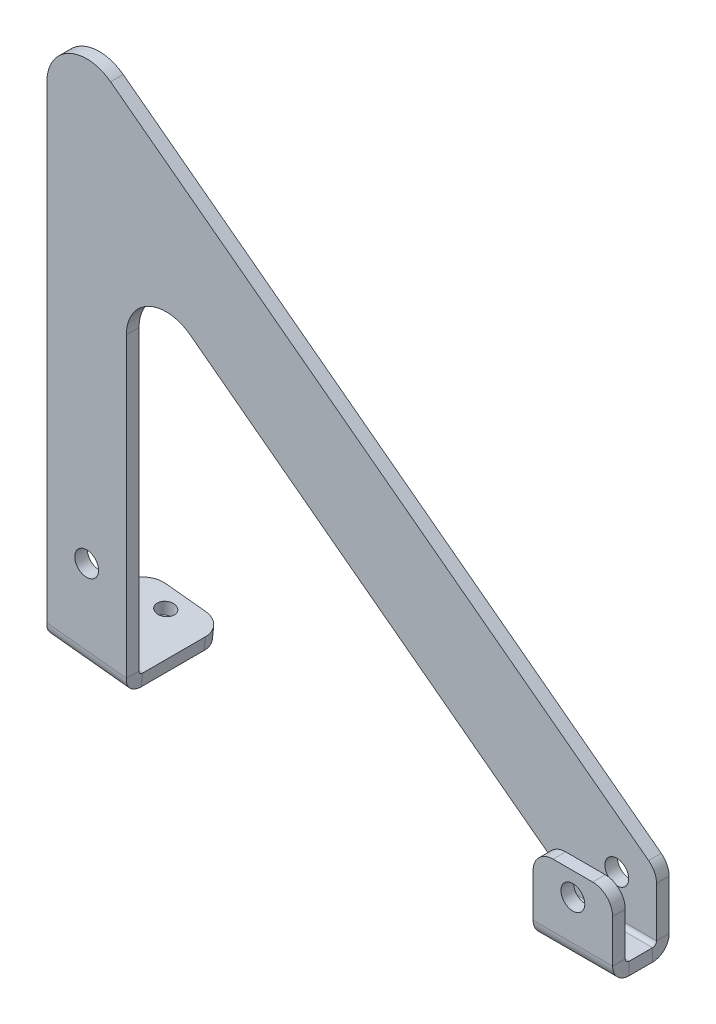
SolidWorks part; units mm, degrees
note: The reader was unsure of these and kept them because the rebuilt part matched: flange length of "Edge-Flange3", "Edge-Flange4", "Edge-Flange5".
ref_plane "Front Plane" through (0, 0, 0) normal (0, 0, 1) x (1, 0, 0)
ref_plane "Top Plane" through (0, 0, 0) normal (0, 1, 0) x (1, 0, 0)
ref_plane "Right Plane" through (0, 0, 0) normal (1, 0, 0) x (0, 0, -1)
sketch "Sketch1" plane through (0, 0, 0) normal (0, 0, 1) x (1, 0, 0)
  line L0 (0, 0) -> (0, 110) construction
  line L1 (0, 110) -> (141.3585, 3.4787) construction
  line L2 (10, 0) -> (10, 84.9289)
  line L3 (10, 89.9431) -> (130.0262, -0.5031) construction
  line L4 (-10, 0) -> (-10, 130.0569)
  line L5 (-10, 130.0569) -> (143.3721, 14.4827)
  line L6 (-10, 0) -> (10, 0)
  line L8 (123.3721, -0.5031) -> (10, 84.9289)
  line L9 (123.3721, -0.5031) -> (143.3721, -0.5031)
  line L12 (143.3721, -0.5031) -> (143.3721, 14.4827)
  line L15 (-10, 130.0569) -> (147.3766, 11.4651) construction
  line L16 (10, 89.9431) -> (135.3403, -4.5076) construction
  line L17 (10, 0) -> (10, 89.9431) construction
  circle A0 centre (133.3721, 9.4969) radius 3 construction
  circle A1 centre (0, 10) radius 3 construction
  dimension "D8" = 6
  dimension "D1" = 110
  dimension "D2" = 177
  dimension "D3" = 53
  dimension "D6" = 10
  dimension "D7" = 10
  dimension "D9" = 10
  dimension "D10" = 10
  dimension "D11" = 20
  dimension "D4" = 10
  dimension "D5" = 10
base flange "Base-Flange1" sketch "Sketch1" thickness 3.175 reverse thickness direction no parameters "D1"=1
sketch "Sketch12" plane through (0, 0, 0) normal (0, 0, 1) x (1, 0, 0)
  line L0 (-10, 0) -> (10, 0) construction
  line L1 (0, 10) -> (0, 110)
  line L2 (0, 110) -> (133.3721, 9.4969)
  line L3 (143.3721, 14.4827) -> (-10, 130.0569) construction
  circle A0 centre (133.3721, 9.4969) radius 3
  circle A1 centre (0, 10) radius 3
  dimension "D3" = 6
  dimension "D1" = 10
  dimension "D2" = 100
  dimension "D4" = 167
edge flange "Edge-Flange3" sketch "Sketch15" flange angle 90 flange length 14.23 flange position bend outside bend radius 1 thickness 3.175 parameters "D6"=10
sketch "Sketch15" plane through (0, -0.5031, 0) normal (0, -1, 0) x (1, 0, 0)
  line L0 (123.3721, 0) -> (143.3721, 0) construction
  line L1 (123.3721, 0) -> (143.3721, 0)
  line L2 (123.3721, 0) -> (123.3721, 11.055)
  line L3 (123.3721, 11.055) -> (143.3721, 11.055)
  line L4 (143.3721, 11.055) -> (143.3721, 0)
bend "EdgeBend3" bend radius 1 bend angle 90 parameters "D5"=1
edge flange "Edge-Flange4" sketch "Sketch18" flange angle 90 flange length 20 flange position material inside bend radius 1 thickness 3.175 parameters "D6"=10
sketch "Sketch18" plane through (0, -1.5031, 11.055) normal (0, 0, 1) x (1, 0, 0)
  line L0 (143.3721, 0) -> (123.3721, 0) construction
  line L1 (143.3721, 0) -> (123.3721, 0)
  line L2 (123.3721, 0) -> (123.3721, 16.825)
  line L3 (123.3721, 16.825) -> (143.3721, 16.825)
  line L4 (143.3721, 16.825) -> (143.3721, 0)
bend "EdgeBend4" bend radius 1 bend angle 90 parameters "D5"=2
extrude "Cut-Extrude1" cut sketch "Sketch12" along normal through all both and the other way through all contours A0 | A1
sketch "Sketch19" plane through (0, 0, 0) normal (0, 0, 1) x (1, 0, 0)
  line L0 (-10, 0) -> (10, 0)
  line L1 (-10, 0) -> (-10, -7.8979)
  line L2 (10, 0) -> (10, -10)
  line L3 (-10, -7.8979) -> (10, -10)
  point P0 (-10, -6.9136)
  dimension "D1" = 10
  dimension "D2" = 84
base flange "Tab1" sketch "Sketch19" thickness 3.175 reverse thickness direction no parameters "D1"=1
edge flange "Edge-Flange5" sketch "Sketch24" flange angle 90 flange length 25 flange position bend outside bend radius 1 thickness 3.175 parameters "D6"=10
sketch "Sketch24" plane through (-0.9303, -8.8512, -3.175) normal (-0.1045, -0.9945, 0) x (-0.9945, 0.1045, 0)
  line L0 (9.1197, 0) -> (-10.9905, 0) construction
  line L1 (9.1197, 0) -> (-10.9905, 0)
  line L2 (-10.9905, 0) -> (-10.9905, 21.825)
  line L3 (-10.9905, 21.825) -> (9.1197, 21.825)
  line L4 (9.1197, 21.825) -> (9.1197, 0)
bend "EdgeBend5" bend radius 1 bend angle 90 parameters "D5"=3
fillet "Fillet1" radius 10 2 edges at (-10, 130.0569, -1.5875) (10, 84.9289, -1.5875)
fillet "Fillet2" radius 5 5 edges at (143.3721, 14.4827, -1.5875) (123.3721, 15.3219, 9.4675) (143.3721, 15.3219, 9.4675) (-10.2705, -10.4712, -25) (9.7295, -12.5733, -25)
sketch "Sketch27" plane through (-1.0348, -9.8457, 0) normal (0.1045, 0.9945, 0) x (0.9945, -0.1045, 0)
  line L4 (5.9905, 25) -> (-4.1197, 25)
  line L5 (-9.1197, 20) -> (-9.1197, 4.175)
  line L6 (-9.1197, 4.175) -> (10.9905, 4.175)
  line L7 (10.9905, 4.175) -> (10.9905, 20)
  line L8 (5.9905, 25) -> (-4.1197, 25)
  line L9 (-9.1197, 20) -> (-9.1197, 4.175)
  line L10 (-9.1197, 4.175) -> (10.9905, 4.175)
  line L11 (10.9905, 4.175) -> (10.9905, 20)
  circle A1 centre (0.9354, 20) radius 2.1554
  arc A2 (-4.1197, 25) -> (-9.1197, 20) centre (-4.1197, 20) ccw
  arc A3 (10.9905, 20) -> (5.9905, 25) centre (5.9905, 20) ccw
  arc A4 (-4.1197, 25) -> (-9.1197, 20) centre (-4.1197, 20) ccw
  arc A5 (10.9905, 20) -> (5.9905, 25) centre (5.9905, 20) ccw
  circle A6 centre (0.9354, 10) radius 2.1554
  point P15 (0.9354, 25)
  dimension "D2" = 4.3108
  dimension "D3" = 10
  dimension "D4" = 5
  dimension "D1" = 0
extrude "Cut-Extrude2" cut sketch "Sketch27" against normal through all contours A1 | A6
sketch "Bend-Lines1" [suppressed] plane through (0, 0, 0) normal (0, 1, 0) x (1, 0, 0)
sketch "Bounding-Box1" [suppressed] plane through (0, 0, 0) normal (0, 1, 0) x (1, 0, 0)
sheet metal parameters "Sheet-Metal1" thickness 3.175 parameters "D1"=1
flat pattern "Flat-Pattern1" [suppressed]
sketch "Bend-Lines2" plane through (0, 0, 0) normal (0, 1, 0) x (1, 0, 0)
sketch3d "Bounding-Box2" [suppressed]
  line L0 (-10, 130.0569, 0) -> (143.8624, 129.4765, 0) construction
  line L1 (-10.4906, 0.0019, 0) -> (143.3718, -0.5786, 0) construction
  line L2 (-10, 130.0569, 0) -> (-10.4906, 0.0019, 0) construction
  line L3 (143.8624, 129.4765, 0) -> (143.3718, -0.5786, 0) construction
sheet metal parameters "Sheet-Metal4" thickness 3.175 parameters "D1"=1
flat pattern "Flat-Pattern1"
sketch "Bend-Lines2" plane through (0, 0, 0) normal (0, 0, 1) x (1, 0, 0)
  line L0 (143.3721, 1.6397) -> (123.3721, 1.6397) construction
  line L1 (143.3721, 1.6397) -> (123.3721, 1.6397) construction
sketch3d "Bounding-Box2" [suppressed]
  line L0 (-10, 130.0569, 0) -> (153.3759, 117.259, 0) construction
  line L1 (-20.1257, 0.7932, 0) -> (143.2502, -12.0047, 0) construction
  line L2 (-10, 130.0569, 0) -> (-20.1257, 0.7932, 0) construction
  line L3 (153.3759, 117.259, 0) -> (143.2502, -12.0047, 0) construction
bend of the flat pattern "Flatten-<EdgeBend3>1"
sheet metal parameters "Sheet-Metal5" thickness 3.175 parameters "D1"=1
flat pattern "Flat-Pattern1"
sketch "Bend-Lines2" plane through (0, 0, 0) normal (0, 0, 1) x (1, 0, 0)
  line L0 (123.3721, -2.5353) -> (143.3721, -2.5353) construction
  line L1 (123.3721, -2.5353) -> (143.3721, -2.5353) construction
  line L2 (123.3721, -12.4798) -> (143.3721, -12.4798) construction
  line L3 (123.3721, -12.4798) -> (143.3721, -12.4798) construction
sketch3d "Bounding-Box2" [suppressed]
  line L0 (-10, 130.0569, 0) -> (164.9139, -1.7501, 0) construction
  line L1 (-72.5094, 47.1042, 0) -> (102.4045, -84.7029, 0) construction
  line L2 (-10, 130.0569, 0) -> (-72.5094, 47.1042, 0) construction
  line L3 (164.9139, -1.7501, 0) -> (102.4045, -84.7029, 0) construction
bend of the flat pattern "Flatten-<EdgeBend3>1"
bend of the flat pattern "Flatten-<EdgeBend4>1"
sheet metal parameters "Sheet-Metal6" thickness 3.175 parameters "D1"=1
flat pattern "Flat-Pattern1"
sketch "Bend-Lines2" plane through (0, 0, 0) normal (0, 0, 1) x (1, 0, 0)
  line L0 (123.3721, -2.5353) -> (143.3721, -2.5353) construction
  line L1 (123.3721, -2.5353) -> (143.3721, -2.5353) construction
  line L2 (123.3721, -12.4798) -> (143.3721, -12.4798) construction
  line L3 (123.3721, -12.4798) -> (143.3721, -12.4798) construction
sketch3d "Bounding-Box2" [suppressed]
  line L0 (-10, 130.0569, 0) -> (164.9139, -1.7501, 0) construction
  line L1 (-71.3043, 48.7033, 0) -> (103.6095, -83.1037, 0) construction
  line L2 (-10, 130.0569, 0) -> (-71.3043, 48.7033, 0) construction
  line L3 (164.9139, -1.7501, 0) -> (103.6095, -83.1037, 0) construction
bend of the flat pattern "Flatten-<EdgeBend3>1"
bend of the flat pattern "Flatten-<EdgeBend4>1"
sheet metal parameters "Sheet-Metal7" thickness 3.175 parameters "D1"=1
flat pattern "Flat-Pattern7"
sketch "Bend-Lines3" plane through (0, 0, 0) normal (0, 0, 1) x (1, 0, 0)
  line L0 (123.3721, -12.4798) -> (143.3721, -12.4798) construction
  line L1 (123.3721, -2.5353) -> (143.3721, -2.5353) construction
  line L2 (123.3721, -12.4798) -> (143.3721, -12.4798) construction
  line L3 (123.3721, -2.5353) -> (143.3721, -2.5353) construction
sketch3d "Bounding-Box3" [suppressed]
  line L0 (-10, 130.0569, 0) -> (163.7887, 103.5571, 0) construction
  line L1 (-30.871, -6.8175, 0) -> (142.9177, -33.3173, 0) construction
  line L2 (-10, 130.0569, 0) -> (-30.871, -6.8175, 0) construction
  line L3 (163.7887, 103.5571, 0) -> (142.9177, -33.3173, 0) construction
bend of the flat pattern "Flatten-<EdgeBend4>2"
bend of the flat pattern "Flatten-<EdgeBend3>2"
sheet metal parameters "Sheet-Metal8" thickness 3.175 parameters "D1"=1
flat pattern "Flat-Pattern7"
sketch "Bend-Lines3" plane through (0, 0, 0) normal (0, 0, 1) x (1, 0, 0)
  line L0 (123.3721, -12.4798) -> (143.3721, -12.4798) construction
  line L1 (123.3721, -2.5353) -> (143.3721, -2.5353) construction
  line L2 (123.3721, -12.4798) -> (143.3721, -12.4798) construction
  line L3 (123.3721, -2.5353) -> (143.3721, -2.5353) construction
  line L4 (-10.0058, -7.846) -> (9.776, -5.7669) construction
  line L5 (-10.0058, -7.846) -> (9.776, -5.7669) construction
sketch3d "Bounding-Box3" [suppressed]
  line L0 (143.3721, 130.0569, 0) -> (143.3721, -30.601, 0) construction
  line L1 (-10.0116, 130.0569, 0) -> (-10.0116, -30.601, 0) construction
  line L2 (143.3721, 130.0569, 0) -> (-10.0116, 130.0569, 0) construction
  line L3 (143.3721, -30.601, 0) -> (-10.0116, -30.601, 0) construction
bend of the flat pattern "Flatten-<EdgeBend4>2"
bend of the flat pattern "Flatten-<EdgeBend3>2"
bend of the flat pattern "Flatten-<EdgeBend5>1"
sheet metal parameters "Sheet-Metal9" thickness 3.175 parameters "D1"=1
flat pattern "Flat-Pattern7"
sketch "Bend-Lines3" plane through (0, 0, 0) normal (0, 0, 1) x (1, 0, 0)
  line L0 (123.3721, -12.4798) -> (143.3721, -12.4798) construction
  line L1 (123.3721, -2.5353) -> (143.3721, -2.5353) construction
  line L2 (123.3721, -12.4798) -> (143.3721, -12.4798) construction
  line L3 (123.3721, -2.5353) -> (143.3721, -2.5353) construction
  line L4 (-10.2124, -9.919) -> (9.7876, -12.0211) construction
  line L5 (-10.2124, -9.919) -> (9.7876, -12.0211) construction
sketch3d "Bounding-Box3" [suppressed]
  line L0 (-9.8465, 120.1512, 0) -> (145.5532, 117.7835, 0) construction
  line L1 (-12.1955, -34.0275, 0) -> (143.2042, -36.3951, 0) construction
  line L2 (-9.8465, 120.1512, 0) -> (-12.1955, -34.0275, 0) construction
  line L3 (145.5532, 117.7835, 0) -> (143.2042, -36.3951, 0) construction
bend of the flat pattern "Flatten-<EdgeBend4>2"
bend of the flat pattern "Flatten-<EdgeBend3>2"
bend of the flat pattern "Flatten-<EdgeBend5>1"
